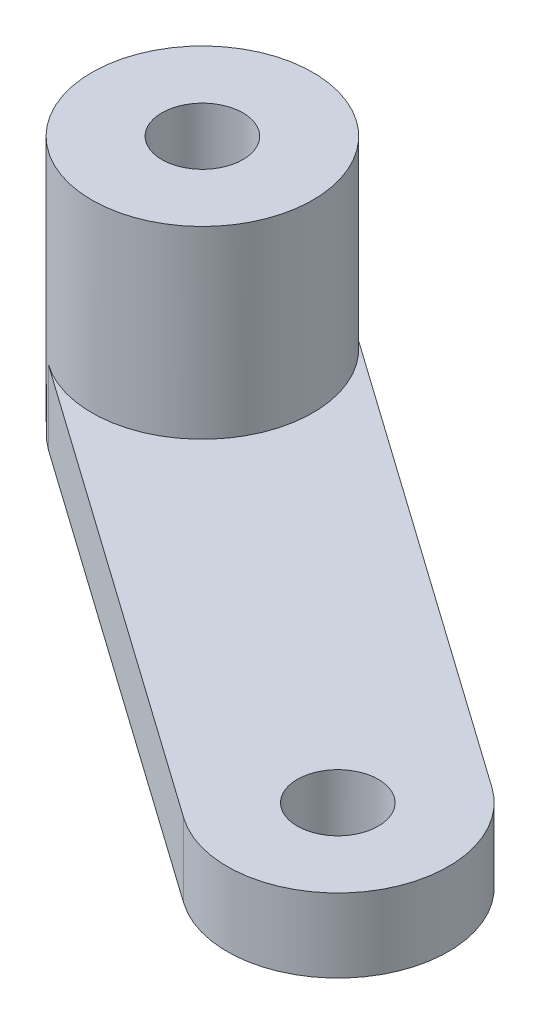
SolidWorks part; units mm, degrees
ref_plane "Front Plane" through (0, 0, 0) normal (0, 0, 1) x (1, 0, 0)
ref_plane "Top Plane" through (0, 0, 0) normal (0, 1, 0) x (1, 0, 0)
ref_plane "Right Plane" through (0, 0, 0) normal (1, 0, 0) x (0, 0, -1)
sketch "Sketch1" plane through (0, 0, 0) normal (0, 1, 0) x (1, 0, 0)
  line L1 (-15.7698, 16.2758) -> (-19.2302, 11.3742) construction
  line L2 (-12.5, 0) -> (12.5, 0) construction
  line L3 (0, 12.5) -> (0, -12.5) construction
  line L4 (-3.2698, 7.4508) -> (-6.7302, 2.5492) construction
  line L5 (-15.7698, 16.2758) -> (-3.2698, 7.4508)
  line L6 (-19.2302, 11.3742) -> (-6.7302, 2.5492)
  arc A0 (-6.7302, 2.5492) -> (-3.2698, 7.4508) centre (-5, 5) ccw
  arc A1 (-15.7698, 16.2758) -> (-19.2302, 11.3742) centre (-17.5, 13.825) ccw
  point P7 (0, 0)
  point P16 (0, 0)
  dimension "D1" = 6
  dimension "D2" = 15.3013
  dimension "D3" = 25
  dimension "D4" = 5
  dimension "D5" = 5
  dimension "D6" = 13.825
  dimension "D7" = 17.5
extrude "Boss-Extrude1" add sketch "Sketch1" along normal blind 2
sketch "Sketch2" plane through (0, 2, 0) normal (0, 1, 0) x (1, 0, 0)
  circle A0 centre (-17.5, 13.825) radius 3
  circle A1 centre (-17.5, 13.825) radius 1.1
  dimension "D1" = 2.2
  dimension "D2" = 6
extrude "Boss-Extrude2" add sketch "Sketch2" along normal blind 5
sketch "Sketch4" plane through (0, 0, 0) normal (0, -1, 0) x (1, 0, 0)
  circle A0 centre (-5, -5) radius 1.1
  circle A1 centre (-17.5, -13.825) radius 1.1
  dimension "D1" = 2.2
extrude "Cut-Extrude1" cut sketch "Sketch4" against normal blind 5
